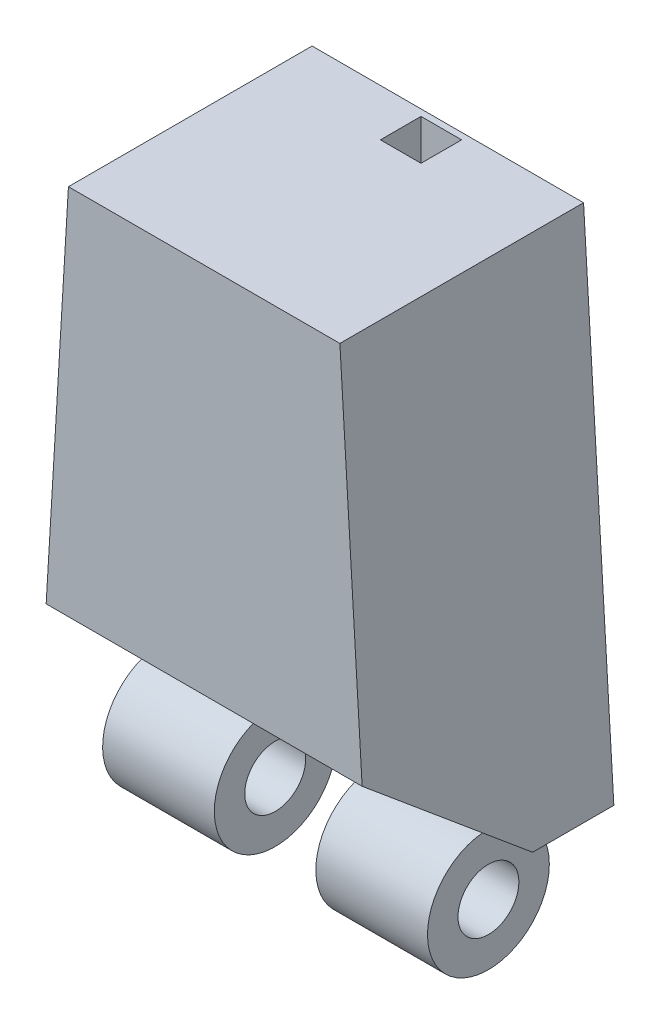
SolidWorks part; units mm, degrees
ref_plane "Front Plane" through (0, 0, 0) normal (0, 0, 1) x (1, 0, 0)
ref_plane "Top Plane" through (0, 0, 0) normal (0, 1, 0) x (1, 0, 0)
ref_plane "Right Plane" through (0, 0, 0) normal (1, 0, 0) x (0, 0, -1)
sketch "Sketch1" plane through (0, 0, 0) normal (0, 0, 1) x (1, 0, 0)
  line L0 (-56.5743, 0) -> (-40.2208, 0)
  line L2 (-56.5743, 0) -> (-55.0819, 24.9554)
  line L3 (-40.2208, 0) -> (-41.7131, 24.9554)
  arc A0 (-41.7131, 24.9554) -> (-55.0819, 24.9554) centre (-48.3975, 24.9554) ccw
extrude "Boss-Extrude1" add sketch "Sketch1" along normal blind 12
sketch "Sketch2" plane through (0, 0, 12) normal (0, 0, 1) x (1, 0, 0)
  line L0 (-40.2208, 0) -> (-56.5743, 0)
  line L1 (-48.3975, 0) -> (-48.3975, 29.5391)
ref_plane "Plane1" through (-48.3975, 0, 0) normal (1, 0, 0) x (0, 0, -1)
sketch "Sketch3" plane through (-48.3975, 0, 0) normal (1, 0, 0) x (0, 0, -1)
  line L0 (0, 0) -> (-4, 0)
  line L1 (-12, 0) -> (0, 0) construction
  line L2 (-4, 0) -> (-12, 6.614)
  line L3 (-12, 0) -> (-12, 24.9554) construction
  line L4 (-12, 6.614) -> (-12, 0)
  line L5 (-12, 0) -> (-4, 0)
extrude "Cut-Extrude1" cut sketch "Sketch3" against normal through all both and the other way through all contours L4 L5 L2 region at (-48.3975, 2.2047, 9.3333)
sketch "Sketch6" plane through (-48.3975, 0, 0) normal (1, 0, 0) x (0, 0, -1)
  line L1 (0, 0) -> (-12, 0)
  line L2 (-6, 0) -> (-6, -1.1)
  circle A0 centre (-6, -1.1) radius 1.5
  circle A1 centre (-6, -1.1) radius 3
extrude "Boss-Extrude2" add sketch "Sketch6" along normal mid plane 16 contours L1 A1 A0 | L1 A1 A0 region at (-48.3975, -0.5537, 3.1241) region at (-48.3975, 0.8343, 6)
extrude "Cut-Extrude2" cut sketch "Sketch6<3>" against normal mid plane 5 contours L1 A1 A0 | L1 A1 A0 region at (-48.3975, -0.5537, 3.1241) region at (-48.3975, 0.8343, 6)
sketch "Sketch6<3>" plane through (-48.3975, 0, 0) normal (1, 0, 0) x (0, 0, -1) same geometry as "Sketch6"
sketch "Sketch7" plane through (-48.3975, 0, 0) normal (1, 0, 0) x (0, 0, -1)
  line L0 (-7.1617, 2.6139) -> (-11.0152, 5.7998)
  line L1 (-4, 0) -> (-12, 6.614) construction
  line L2 (-7.1617, 2.6139) -> (-3.9757, 6.4674)
  line L3 (-3.9757, 6.4674) -> (-7.8293, 9.6534)
  line L4 (-7.8293, 9.6534) -> (-11.0152, 5.7998)
  line L5 (-12, 6.614) -> (-4, 0) construction
extrude "Cut-Extrude3" cut sketch "Sketch7" against normal mid plane 10
sketch "Sketch8" plane through (-48.3975, 0, 0) normal (1, 0, 0) x (0, 0, -1)
  circle A0 centre (-7.5481, 6.1771) radius 1.5
extrude "Boss-Extrude3" add sketch "Sketch8" along normal mid plane 11
sketch "Sketch9" plane through (-48.3975, 0, 0) normal (1, 0, 0) x (0, 0, -1)
  line L1 (-12, 31.6398) -> (0, 31.6398)
  line L2 (-12, 31.6398) -> (-12, 24.9554)
  line L3 (-12, 24.9554) -> (0, 24.9554)
  line L4 (0, 31.6398) -> (0, 24.9554)
extrude "Cut-Extrude4" cut sketch "Sketch9" against normal through all both and the other way through all
sketch "Sketch10" plane through (-48.3975, 0, 0) normal (1, 0, 0) x (0, 0, -1)
  line L0 (0, 0) -> (-2.32, 0)
  line L1 (-4, 0) -> (0, 0) construction
  line L2 (-2.32, 0) -> (-2.32, 28.5504)
  line L3 (-2.32, 28.5504) -> (-0.32, 28.5504)
  line L4 (-0.32, 28.5504) -> (-0.32, 0)
extrude "Cut-Extrude5" cut sketch "Sketch10" against normal mid plane 2 contours L4 L3 L2 L0 region at (-48.3975, 14.2752, 1.32)
